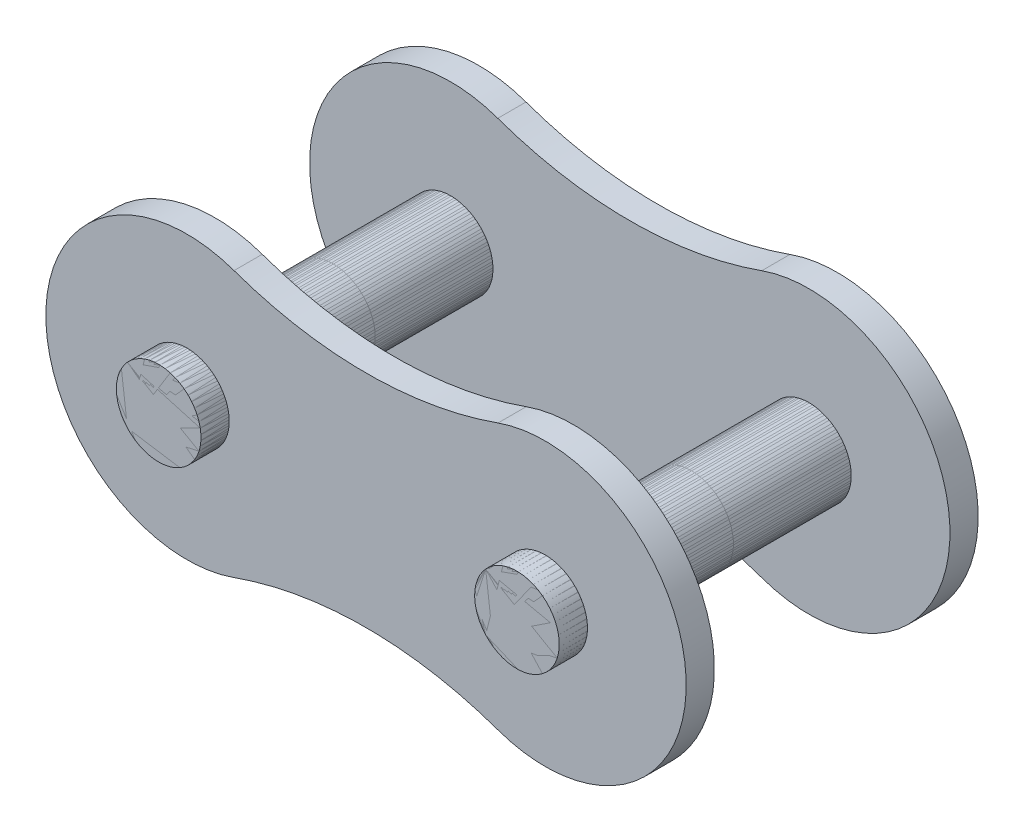
SolidWorks part; units mm, degrees
material "AISI 304"
ref_plane "Plane1" through (0, 0, 0) normal (0, 0, 1) x (1, 0, 0)
ref_plane "Plane2" through (0, 0, 0) normal (0, 1, 0) x (1, 0, 0)
ref_plane "Plane3" through (0, 0, 0) normal (1, 0, 0) x (0, 0, -1)
sketch "Sketch1" plane through (0, 0, 0) normal (0, 0, 1) x (1, 0, 0)
  line L0 (3.175, 2.6048) -> (3.175, -2.6048) construction
  arc A0 (0.8355, 2.3562) -> (0.8355, -2.3562) centre (0, 0) ccw
  circle A4 centre (0, 0) radius 0.75
  circle A8 centre (6.35, 0) radius 0.75
  arc A9 (5.5145, 2.3562) -> (5.5145, -2.3562) centre (6.35, 0) cw
  arc A10 (0.8355, 2.3562) -> (5.5145, 2.3562) centre (3.175, 8.9537) ccw
  arc A11 (0.8355, -2.3562) -> (5.5145, -2.3562) centre (3.175, -8.9537) cw
  dimension "D1" = 5
  dimension "D2" = 3.175
  dimension "D6" = 1.5
  dimension "D3" = 7
extrude "Boss-Extrude1" add sketch "Sketch1" along normal blind 0.5
sketch "Sketch2" plane through (0, 0, 0) normal (0, 0, -1) x (-1, 0, 0)
  circle A0 centre (-6.35, 0) radius 0.75
  circle A1 centre (0, 0) radius 0.75
  dimension "D1" = 1.5
  dimension "D2" = 1.5
extrude "Boss-Extrude2" add sketch "Sketch2" along normal blind 5.175 and the other way blind 1
ref_plane "Plane4" through (0, 0, -2.0875) normal (0, 0, -1) x (-1, 0, 0)
mirror "Mirror1" about plane through (0, 0, -2.0875) normal (0, 0, -1) of bodies 105 104
